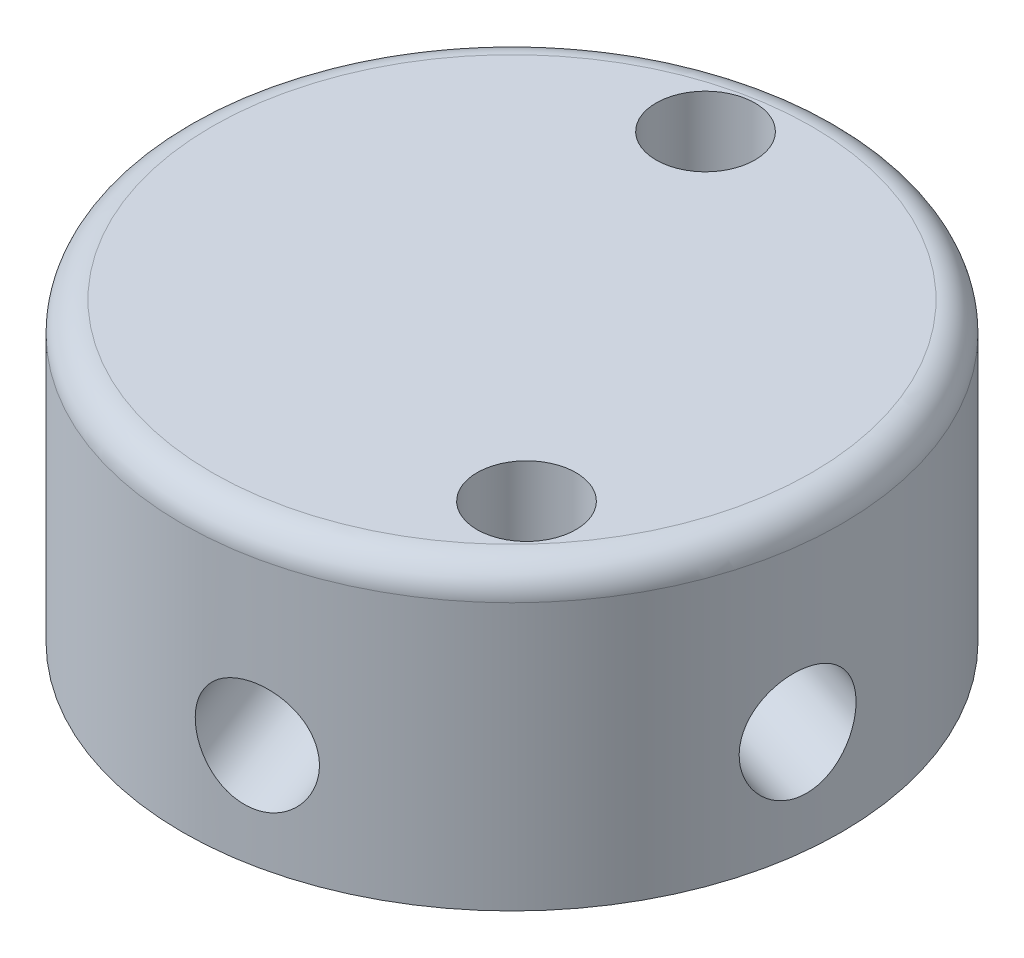
SolidWorks part; units mm, degrees
ref_plane "Front Plane" through (0, 0, 0) normal (0, 0, 1) x (1, 0, 0)
ref_plane "Top Plane" through (0, 0, 0) normal (0, 1, 0) x (1, 0, 0)
ref_plane "Right Plane" through (0, 0, 0) normal (1, 0, 0) x (0, 0, -1)
sketch "Sketch1" plane through (0, 0, 0) normal (0, 1, 0) x (1, 0, 0)
  circle A0 centre (0, 0) radius 10
  dimension "D1" = 20
extrude "Boss-Extrude1" add sketch "Sketch1" along normal blind 3 and the other way blind 6
ref_axis "5hubaxis" through (0, 5.5, 0) along (0, -1, 0)
ref_plane "holeplane" through (-3.3529, -1.0931, 1.8877) normal (0.8382, 0.2733, -0.4719) x (-0.4487, -0.1463, -0.8816)
sketch "Sketch4" plane through (-3.3529, -1.0931, 1.8877) normal (0.8382, 0.2733, -0.4719) x (-0.4487, -0.1463, -0.8816)
  circle A0 centre (0, 0) radius 1.5 construction
  circle A1 centre (0, 0) radius 1.5 construction
  circle A2 centre (0, 0) radius 1.6
  dimension "D1" = 3.2
extrude "hole" cut sketch "Sketch4" against normal through all
pattern_circular "holecir" count 5 over 360 about axis through (0, 5.5, 0) along (0, -1, 0) of "hole"
fillet "Fillet3" radius 0.9 1 edges at (0, 3, 10)
sketch "Sketch5" plane through (0, -6, 0) normal (0, -1, 0) x (1, 0, 0)
  circle A0 centre (0, 0) radius 3.5
  dimension "D1" = 7
extrude "Cut-Extrude1" cut sketch "Sketch5" against normal blind 2.6
sketch "Sketch6" plane through (0, 3, 0) normal (0, 1, 0) x (1, 0, 0)
  line L0 (0, 0) -> (-7.3586, 6.7713) construction
  line L1 (-1.748, 3.7828) -> (-6.1804, 7.8615) construction
  line L2 (0, 0) -> (4.166, 9.0909) construction
  line L3 (2.6578, 9.6404) -> (0.1484, 4.1645) construction
  line L4 (0, 0) -> (-1.9732, 9.8034) construction
  line L5 (0, 0) -> (9.9333, -1.1528) construction
  line L6 (3.6376, -2.0329) -> (9.6209, -2.7273) construction
  line L7 (0, 0) -> (7.3586, -6.7713) construction
  circle A0 centre (-1.4799, 7.3525) radius 1.5
  circle A1 centre (5.519, -5.0785) radius 1.5
  circle A2 centre (0, 0) radius 7.5 construction
  circle A3 centre (0, 0) radius 10 construction
  point P19 (5.519, -5.0785)
  dimension "D1" = 3
  dimension "D2" = 15
  dimension "D5" = 3
  dimension "D3" = 36
  dimension "D4" = 36
extrude "Cut-Extrude2" cut sketch "Sketch6" against normal through all
